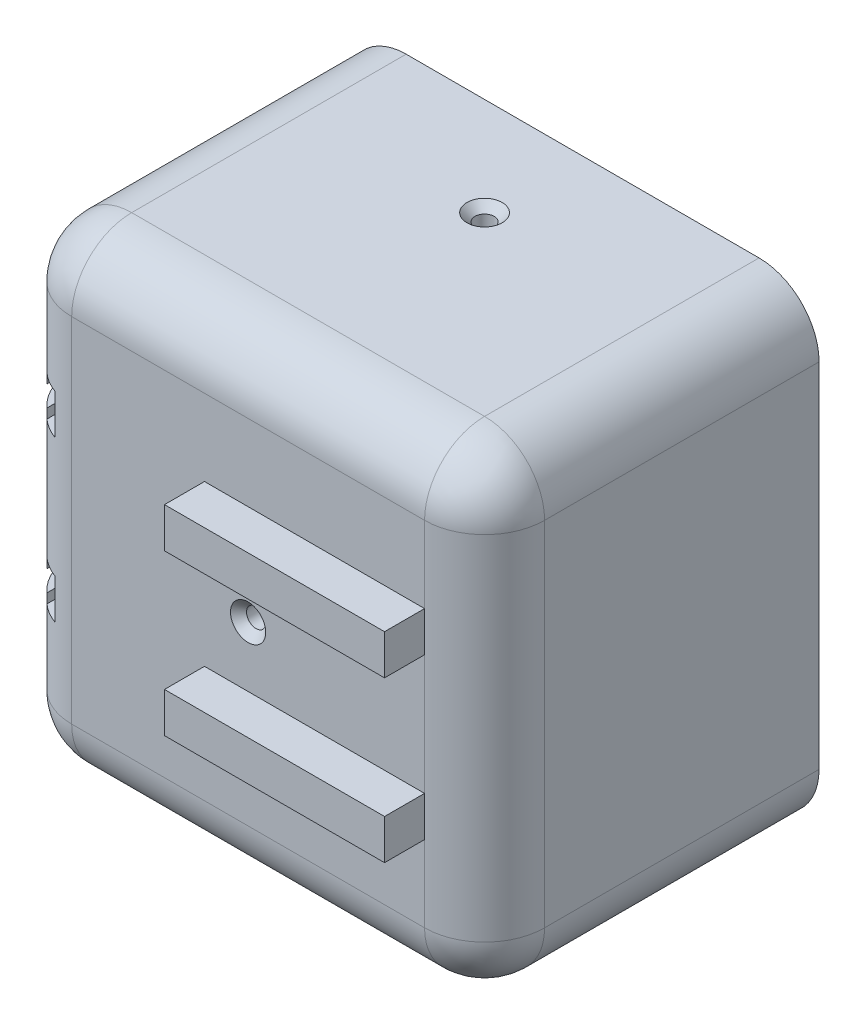
SolidWorks part; units mm, degrees
note: '?' marks a value the reader was unsure of.
ref_plane "Front Plane" through (0, 0, 0) normal (0, 0, 1) x (1, 0, 0)
ref_plane "Top Plane" through (0, 0, 0) normal (0, 1, 0) x (1, 0, 0)
ref_plane "Right Plane" through (0, 0, 0) normal (1, 0, 0) x (0, 0, -1)
sketch "Sketch1" plane through (0, 0, 0) normal (0, 0, 1) x (1, 0, 0)
  line L0 (0, 78.4471) -> (0, -76.9705) construction
  line L1 (-83.0616, 0) -> (77.155, 0) construction
  line L3 (-29.55, 29.55) -> (29.55, 29.55)
  line L4 (-29.55, 29.55) -> (-29.55, -29.55)
  line L5 (-29.55, -29.55) -> (29.55, -29.55)
  line L6 (29.55, 29.55) -> (29.55, -29.55)
  dimension "D1" = 59.1
  dimension "D2" = 59.1
extrude "Boss-Extrude1" add sketch "Sketch1" along normal blind 59.1
ref_plane "Plane9" through (0, 0, 29.55) normal (0, 0, 1) x (1, 0, 0)
ref_plane "Plane1" through (0, -14.775, 14.775) normal (0, -0.7071, 0.7071) x (1, 0, 0)
ref_axis "Axis1" through (-29.55, 29.55, 59.1) along (0.5774, -0.5774, -0.5774)?
ref_plane "Plane2" through (0, 0, 0) normal (-0.5774, -0.5774, 0.5774) x (0.8165, -0.4082, 0.4082)
ref_plane "Plane3" through (-19.7, -19.7, 19.7) normal (0.5774, 0.5774, -0.5774) x (-0.8165, 0.4082, -0.4082)
ref_plane "Plane4" through (-9.85, -9.85, 9.85) normal (-0.5774, -0.5774, 0.5774) x (0.8165, -0.4082, 0.4082)
ref_plane "Plane6" through (0, 0, 29.55) normal (0, 0, -1) x (-1, 0, 0)
ref_plane "Plane10" through (0, 0, 29.55) normal (0, 0, -1) x (-1, 0, 0)
ref_plane "Plane11" through (0, 0, 19.55) normal (0, 0, -1) x (-1, 0, 0)
sketch "Sketch2" plane through (-13.4004, -13.4004, 19.55) normal (0, 0, 1) x (0.9659, -0.2588, 0)
  line L1 (73.4206, 63.196) -> (-42.9368, 63.196)
  line L2 (73.4206, 63.196) -> (73.4206, -31.2358)
  line L3 (73.4206, -31.2358) -> (-42.9368, -31.2358)
  line L4 (-42.9368, 63.196) -> (-42.9368, -31.2358)
extrude "Cut-Extrude1" cut sketch "Sketch2" against normal through all from offset 2.25 offset against normal yes
ref_plane "Plane5" through (-39.4, -39.4, 39.4) normal (-0.5774, -0.5774, 0.5774) x (-0.8165, 0.4082, -0.4082)
fillet "Fillet1" radius 7.5 8 edges at (0, -29.55, 59.1) (29.55, 0, 59.1) (29.55, -29.55, 38.2) (-29.55, -29.55, 38.2) (-29.55, 0, 59.1) (0, 29.55, 59.1) (-29.55, 29.55, 38.2) (29.55, 29.55, 38.2)
shell "Shell1" thickness 2.5
ref_plane "Plane7" through (-9.8314, 1.2497, 53.5942) normal (0.4082, -0.8165, -0.4082) x (-0.9129, -0.3651, -0.1826)
sketch "Sketch14" plane through (0, 0, 59.1) normal (0, 0, 1) x (1, 0, 0)
  line L0 (-29.55, -8.7) -> (-27.05, -8.7)
  line L1 (-27.05, -8.7) -> (-27.05, -7.5)
  line L2 (-27.05, -7.5) -> (-24.55, -7.5)
  line L3 (-24.55, -7.5) -> (-24.55, -12.5)
  line L4 (-24.55, -12.5) -> (-27.05, -12.5)
  line L5 (-27.05, -12.5) -> (-27.05, -11.3)
  line L6 (-27.05, -11.3) -> (-29.55, -11.3)
  line L7 (-29.55, -11.3) -> (-29.55, -8.7)
  line L8 (-29.55, -22.05) -> (-29.55, 22.05) construction
  line L9 (-42.181, -10) -> (-13.3805, -10) construction
  line L10 (-43.1184, 0) -> (38.5678, 0) construction
  line L11 (-29.55, 11.3) -> (-29.55, 8.7)
  line L12 (-27.05, 11.3) -> (-29.55, 11.3)
  line L13 (-27.05, 12.5) -> (-27.05, 11.3)
  line L14 (-24.55, 12.5) -> (-27.05, 12.5)
  line L15 (-24.55, 7.5) -> (-24.55, 12.5)
  line L16 (-27.05, 7.5) -> (-24.55, 7.5)
  line L17 (-27.05, 8.7) -> (-27.05, 7.5)
  line L18 (-29.55, 8.7) -> (-27.05, 8.7)
  dimension "D1" = 2.6
  dimension "D2" = 5
  dimension "D3" = 2.5
  dimension "D4" = 2.5
  dimension "D5" = 10
extrude "Cut-Extrude7" cut sketch "Sketch14" against normal blind 35
sketch "Sketch18" plane through (0, -27.05, 0) normal (0, 1, 0) x (1, 0, 0)
  circle A0 centre (-22.05, -51.6) radius 5
  dimension "D1" = 10
extrude "Boss-Extrude2" add sketch "Sketch18" along normal blind 3
sketch "Sketch17" plane through (0, -29.55, 0) normal (0, -1, 0) x (1, 0, 0)
  circle A0 centre (-22.05, 51.6) radius 1.5
  dimension "D1" = 3
extrude "Cut-Extrude10" cut sketch "Sketch17" against normal blind 10
ref_plane "Plane8" through (0, -6.5, 0) normal (0, -1, 0) x (-1, 0, 0)
ref_axis "Axis2" through (-22.05, -24.05, 51.6) along (0, -1, 0)?
sketch "Sketch20" plane through (0, -29.55, 0) normal (0, -1, 0) x (1, 0, 0)
  line L0 (-36.3458, 37.3042) -> (-9.0033, 64.6467) construction
  line L1 (22.05, 51.6) -> (-20.55, 51.6) construction
  line L2 (-34.1921, 63.7421) -> (-5.1828, 34.7328) construction
  line L3 (-22.6479, 52.9757) -> (-23.0721, 53.4)
  line L4 (-23.0721, 53.4) -> (-23.85, 52.6221)
  line L5 (-23.85, 52.6221) -> (-23.4257, 52.1979)
  line L6 (-21.0279, 49.8) -> (-21.4521, 50.2243)
  line L7 (-20.25, 50.5779) -> (-21.0279, 49.8)
  line L8 (-20.6743, 51.0021) -> (-20.25, 50.5779)
  arc A0 (-22.6479, 52.9757) -> (-23.4257, 52.1979) centre (-22.05, 51.6) ccw
  arc A1 (-20.6743, 51.0021) -> (-21.4521, 50.2243) centre (-22.05, 51.6) cw
  point P9 (-22.86, 53.1878)
  dimension "D2" = 3
  dimension "D1" = 45
  dimension "D3" = 1.1
  dimension "D4" = 0.6
extrude "Cut-Extrude11" cut sketch "Sketch20" against normal up to next
hole_wizard "CSK SLOT for M2 Countersunk Flat Head Screw1" positions "Sketch21" profile "Sketch22" size "M2" standard "ISO" slot yes end condition through all
sketch "Sketch21" plane through (0, 29.55, 0) normal (0, -1, 0) x (0, 0, 1)
  line L2 (-23.1275, 0) -> (23.1275, 0) construction
  line L3 (29.55, 24.2) -> (29.55, -24.2) construction
  point P0 (29.55, 0)
sketch "Sketch22" plane through (0, 29.55, 29.55) normal (1, 0, 0) x (0, 0, 1)
  line L0 (0, 0) -> (0, 59.1)
  line L1 (0, 59.1) -> (1.2, 59.1)
  line L2 (1.2, 59.1) -> (1.2, 1)
  line L3 (1.2, 1) -> (2.2, 0)
  line L5 (2.2, 0) -> (0, 0)
  line L6 (-1.2, 1) -> (-2.2, 0) construction
  line L11 (0, -6.35) -> (0, 107.95) construction
  dimension "Thru Hole Dia." = 2.4
  dimension "Thru Hole Depth" = 59.1
  dimension "Near C'Sink Dia." = 4.4
  dimension "Near C'Sink Angle" = 90
hole_wizard "CSK SLOT for M2 Countersunk Flat Head Screw2" positions "Sketch23" profile "Sketch24" size "M2" standard "ISO" slot yes end condition through all
sketch "Sketch23" plane through (0, 0, 59.1) normal (0, 0, 1) x (1, 0, 0)
  line L0 (23.1275, 0) -> (-23.1275, 0) construction
  line L2 (0, -23.1275) -> (0, 23.1275) construction
  point P0 (0, 0)
sketch "Sketch24" plane through (0, 0, 59.1) normal (1, 0, 0) x (0, -1, 0)
  line L0 (0, 0) -> (0, 41.8)
  line L1 (0, 41.8) -> (1.2, 41.8)
  line L2 (1.2, 41.8) -> (1.2, 1)
  line L3 (1.2, 1) -> (2.2, 0)
  line L5 (2.2, 0) -> (0, 0)
  line L6 (-1.2, 1) -> (-2.2, 0) construction
  line L11 (0, -6.35) -> (0, 107.95) construction
  dimension "Thru Hole Dia." = 2.4
  dimension "Thru Hole Depth" = 41.8
  dimension "Near C'Sink Dia." = 4.4
  dimension "Near C'Sink Angle" = 90
hole_wizard "CSK SLOT for M2 Countersunk Flat Head Screw3" positions "Sketch25" profile "Sketch26" size "M2" standard "ISO" slot yes end condition through all
sketch "Sketch25" plane through (0, -29.55, 0) normal (0, -1, 0) x (-1, 0, 0)
  line L2 (-32.505, -29.55) -> (32.505, -29.55) construction
  line L4 (0, 23.1275) -> (0, -23.1275) construction
  point P2 (0, -29.55)
sketch "Sketch26" plane through (0, -29.55, 29.55) normal (1, 0, 0) x (0, 0, -1)
  line L0 (0, 0) -> (0, 59.1)
  line L1 (0, 59.1) -> (1.2, 59.1)
  line L2 (1.2, 59.1) -> (1.2, 1)
  line L3 (1.2, 1) -> (2.2, 0)
  line L5 (2.2, 0) -> (0, 0)
  line L6 (-1.2, 1) -> (-2.2, 0) construction
  line L11 (0, -6.35) -> (0, 107.95) construction
  dimension "Thru Hole Dia." = 2.4
  dimension "Thru Hole Depth" = 59.1
  dimension "Near C'Sink Dia." = 4.4
  dimension "Near C'Sink Angle" = 90
sketch "Sketch27" plane through (-29.55, 29.55, 0) normal (1, 0, 0) x (0, 0, -1)
  line L0 (-18.3, -59.1) -> (-18.3, -61.7)
  line L1 (-18.3, -61.7) -> (-17.05, -61.7)
  line L2 (-17.05, -61.7) -> (-17.05, -64.2)
  line L3 (-17.05, -64.2) -> (-22.05, -64.2)
  line L4 (-22.05, -64.2) -> (-22.05, -61.7)
  line L5 (-22.05, -61.7) -> (-20.8, -61.7)
  line L6 (-20.8, -61.7) -> (-20.8, -59.1)
  line L7 (-20.8, -59.1) -> (-18.3, -59.1)
  line L8 (-19.55, -57.6612) -> (-19.55, 18.17) construction
  line L9 (-29.55, 2.955) -> (-29.55, -62.055) construction
  line L10 (-50.1, -59.1) -> (-17.3, -59.1) construction
  line L12 (-29.55, -57.6612) -> (-29.55, 18.17) construction
  line L13 (-38.3, -59.1) -> (-40.8, -59.1)
  line L14 (-38.3, -61.7) -> (-38.3, -59.1)
  line L15 (-37.05, -61.7) -> (-38.3, -61.7)
  line L16 (-37.05, -64.2) -> (-37.05, -61.7)
  line L17 (-42.05, -64.2) -> (-37.05, -64.2)
  line L18 (-42.05, -61.7) -> (-42.05, -64.2)
  line L19 (-40.8, -61.7) -> (-42.05, -61.7)
  line L20 (-40.8, -59.1) -> (-40.8, -61.7)
  point P10 (-22.05, -62.95)
  dimension "D1" = 2.5
  dimension "D2" = 5
  dimension "D3" = 2.6
  dimension "D4" = 2.5
  dimension "D5" = 10
extrude "Boss-Extrude3" add sketch "Sketch27" along normal blind 35
sketch "Sketch28" plane through (0, 0, 59.1) normal (0, 0, 1) x (1, 0, 0)
  line L0 (-29.55, -29.55) -> (-29.55, -32.15) construction
  line L1 (-22.05, -29.55) -> (-29.55, -29.55)
  line L2 (-22.05, -29.55) -> (-22.05, -34.65)
  line L3 (-22.05, -34.65) -> (-29.55, -34.65)
  line L4 (-29.55, -29.55) -> (-29.55, -34.65)
  line L5 (5.45, -34.65) -> (-29.55, -34.65) construction
extrude "Cut-Extrude12" cut sketch "Sketch28" against normal through all
sketch "Sketch29" plane through (0, 0, 59.1) normal (0, 0, 1) x (1, 0, 0)
  line L0 (0, 0) -> (22.05, 0) construction
  line L1 (22.05, -22.05) -> (22.05, 22.05) construction
  line L2 (22.05, -7.5) -> (-5.45, -7.5)
  line L3 (22.05, 12.5) -> (-5.45, 12.5)
  line L4 (22.05, 12.5) -> (22.05, 7.5)
  line L5 (22.05, 7.5) -> (-5.45, 7.5)
  line L6 (-5.45, 12.5) -> (-5.45, 7.5)
  line L7 (-5.45, -12.5) -> (-5.45, -7.5)
  line L8 (22.05, -12.5) -> (-5.45, -12.5)
  line L9 (22.05, -12.5) -> (22.05, -7.5)
  dimension "D1" = 27.5
  dimension "D2" = 5
  dimension "D3" = 7.5
extrude "Boss-Extrude4" add sketch "Sketch29" along normal blind 5
